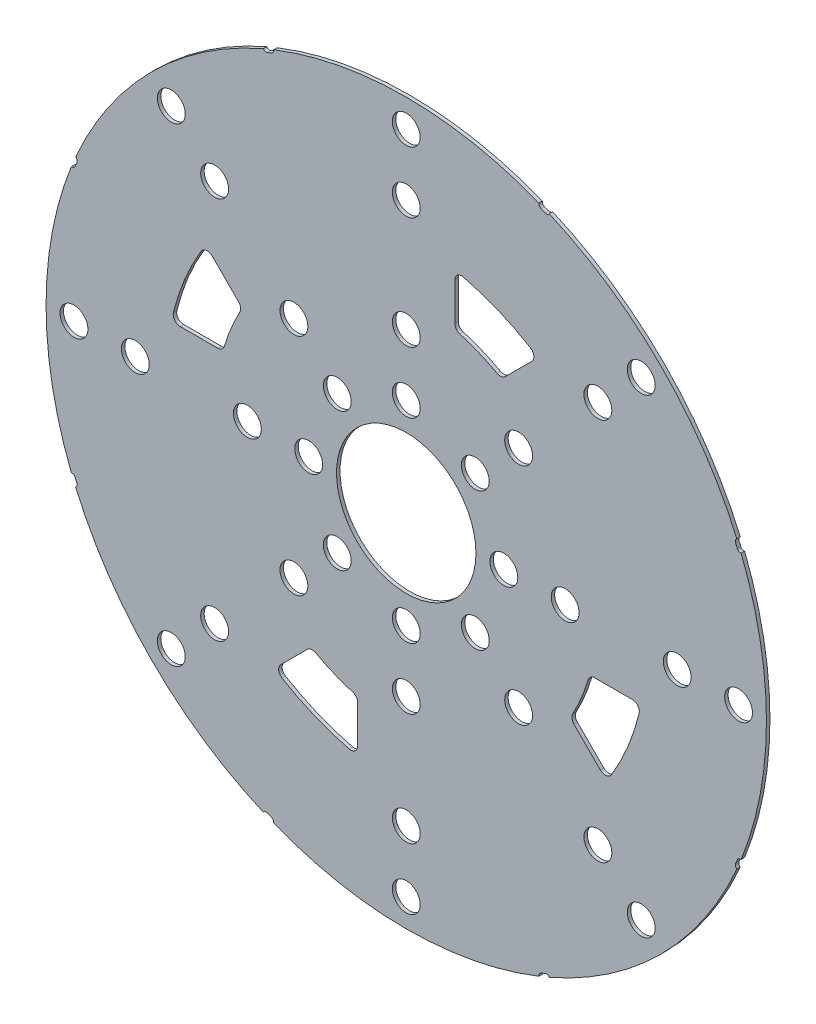
SolidWorks part; units mm, degrees
material "Epoxy, Unfilled"
ref_plane "Front Plane" through (0, 0, 0) normal (0, 0, 1) x (1, 0, 0)
ref_plane "Top Plane" through (0, 0, 0) normal (0, 1, 0) x (1, 0, 0)
ref_plane "Right Plane" through (0, 0, 0) normal (1, 0, 0) x (0, 0, -1)
sketch "Sketch4" plane through (0, 0, 0) normal (0, 0, 1) x (1, 0, 0)
  circle A0 centre (0, 0) radius 82.042
  dimension "D1" = 164.084
extrude "Boss-Extrude2" add sketch "Sketch4" along normal blind 0.7937
sketch "Sketch5" plane through (0, 0, 0.7937) normal (0, 0, 1) x (1, 0, 0)
  circle A0 centre (0, 0) radius 15.875
  dimension "D1" = 31.75
extrude "Cut-Extrude5" cut sketch "Sketch5" against normal through all
sketch "Sketch8" plane through (0, 0, 0.7937) normal (0, 0, 1) x (1, 0, 0)
  line L2 (76.8696, 30.4658) -> (75.8976, 32.8124)
  line L3 (76.8696, 30.4658) -> (75.6963, 29.9798)
  line L4 (75.6963, 29.9798) -> (74.7243, 32.3264)
  line L5 (75.8976, 32.8124) -> (74.7243, 32.3264)
  line L6 (0, 0) -> (82.042, 0) construction
  line L7 (-30.4658, 76.8696) -> (-32.8124, 75.8976)
  line L8 (-30.4658, 76.8696) -> (-29.9798, 75.6963)
  line L9 (-32.8124, 75.8976) -> (-32.3264, 74.7243)
  line L10 (-29.9798, 75.6963) -> (-32.3264, 74.7243)
  line L11 (-32.8124, 75.8976) -> (-29.9798, 75.6963) construction
  line L12 (-30.4658, 76.8696) -> (-32.3264, 74.7243) construction
  line L13 (-75.8976, 32.8124) -> (-76.8696, 30.4658)
  line L14 (-75.8976, 32.8124) -> (-74.7243, 32.3264)
  line L15 (-74.7243, 32.3264) -> (-75.6963, 29.9798)
  line L16 (-76.8696, 30.4658) -> (-75.6963, 29.9798)
  line L17 (-75.8976, 32.8124) -> (-75.6963, 29.9798) construction
  line L18 (-76.8696, 30.4658) -> (-74.7243, 32.3264) construction
  line L19 (-76.8696, -30.4658) -> (-75.8976, -32.8124)
  line L20 (-76.8696, -30.4658) -> (-75.6963, -29.9798)
  line L21 (-75.6963, -29.9798) -> (-74.7243, -32.3264)
  line L22 (-75.8976, -32.8124) -> (-74.7243, -32.3264)
  line L23 (-76.8696, -30.4658) -> (-74.7243, -32.3264) construction
  line L24 (-75.8976, -32.8124) -> (-75.6963, -29.9798) construction
  line L25 (-32.8124, -75.8976) -> (-30.4658, -76.8696)
  line L26 (-32.8124, -75.8976) -> (-32.3264, -74.7243)
  line L27 (-32.3264, -74.7243) -> (-29.9798, -75.6963)
  line L28 (-30.4658, -76.8696) -> (-29.9798, -75.6963)
  line L29 (-32.8124, -75.8976) -> (-29.9798, -75.6963) construction
  line L30 (-30.4658, -76.8696) -> (-32.3264, -74.7243) construction
  line L31 (30.4658, -76.8696) -> (32.8124, -75.8976)
  line L32 (30.4658, -76.8696) -> (29.9798, -75.6963)
  line L33 (29.9798, -75.6963) -> (32.3264, -74.7243)
  line L34 (32.8124, -75.8976) -> (32.3264, -74.7243)
  line L35 (30.4658, -76.8696) -> (32.3264, -74.7243) construction
  line L36 (32.8124, -75.8976) -> (29.9798, -75.6963) construction
  line L37 (75.8976, -32.8124) -> (76.8696, -30.4658)
  line L38 (75.8976, -32.8124) -> (74.7243, -32.3264)
  line L39 (74.7243, -32.3264) -> (75.6963, -29.9798)
  line L40 (76.8696, -30.4658) -> (75.6963, -29.9798)
  line L41 (75.8976, -32.8124) -> (75.6963, -29.9798) construction
  line L42 (76.8696, -30.4658) -> (74.7243, -32.3264) construction
  line L43 (76.8696, 30.4658) -> (74.7243, 32.3264) construction
  line L44 (75.8976, 32.8124) -> (75.6963, 29.9798) construction
  line L45 (32.8124, 75.8976) -> (30.4658, 76.8696)
  line L46 (32.8124, 75.8976) -> (32.3264, 74.7243)
  line L47 (32.3264, 74.7243) -> (29.9798, 75.6963)
  line L48 (30.4658, 76.8696) -> (29.9798, 75.6963)
  line L49 (32.8124, 75.8976) -> (29.9798, 75.6963) construction
  line L50 (30.4658, 76.8696) -> (32.3264, 74.7243) construction
  circle A0 centre (0, 0) radius 82.042 construction
  point P3 (-31.3961, 75.7969)
  point P11 (-75.7969, 31.3961)
  point P15 (75.7969, 31.3961)
  point P20 (-75.7969, -31.3961)
  point P25 (-31.3961, -75.7969)
  point P26 (0, 0)
  point P31 (31.3961, -75.7969)
  point P36 (75.7969, -31.3961)
  point P45 (31.3961, 75.7969)
  point P46 (0, 0)
  dimension "D3" = 0.635
  dimension "D5" = 1.27
  dimension "D6" = 2.54
  dimension "D7" = 1.27
  dimension "D9" = 0.635
  dimension "D10" = 112.5
  dimension "D14" = 0.635
  dimension "D21" = 22.5
  dimension "D11" = 8
extrude "Cut-Extrude11" cut sketch "Sketch8" against normal through all
sketch "Sketch9" plane through (0, 0, 0.7937) normal (0, 0, 1) x (1, 0, 0)
  line L0 (0, 0) -> (75.692, 0) construction
  line L1 (0, 0) -> (53.5223, 53.5223) construction
  line L2 (0, 0) -> (53.5223, -53.5223) construction
  line L3 (21.7035, 37.3292) -> (30.0037, 45.6293)
  line L4 (11.049, 41.7424) -> (11.049, 53.4806)
  line L5 (41.7424, -11.049) -> (53.4806, -11.049)
  line L6 (37.3292, -21.7035) -> (45.6293, -30.0037)
  line L7 (-11.049, -41.7424) -> (-11.049, -53.4806)
  line L8 (-21.7035, -37.3292) -> (-30.0037, -45.6293)
  line L9 (-41.7424, 11.049) -> (-53.4806, 11.049)
  line L10 (-37.3292, 21.7035) -> (-45.6293, 30.0037)
  circle A0 centre (22.225, 0) radius 3.175
  circle A1 centre (36.195, 0) radius 3.175
  circle A2 centre (61.722, 0) radius 3.175
  circle A3 centre (75.692, 0) radius 3.175
  circle A4 centre (0, 0) radius 15.875 construction
  arc A5 (21.7035, 37.3292) -> (11.049, 41.7424) centre (0, 0) ccw
  circle A6 centre (15.7154, -15.7154) radius 3.175
  circle A7 centre (25.5937, -25.5937) radius 3.175
  circle A8 centre (43.644, -43.644) radius 3.175
  circle A9 centre (53.5223, -53.5223) radius 3.175
  circle A10 centre (0, -22.225) radius 3.175
  circle A11 centre (0, -36.195) radius 3.175
  circle A12 centre (0, -61.722) radius 3.175
  circle A13 centre (0, -75.692) radius 3.175
  circle A14 centre (-15.7154, -15.7154) radius 3.175
  circle A15 centre (-25.5937, -25.5937) radius 3.175
  circle A16 centre (-43.644, -43.644) radius 3.175
  circle A17 centre (-53.5223, -53.5223) radius 3.175
  circle A18 centre (-22.225, 0) radius 3.175
  circle A19 centre (-36.195, 0) radius 3.175
  circle A20 centre (-61.722, 0) radius 3.175
  circle A21 centre (-75.692, 0) radius 3.175
  circle A22 centre (-15.7154, 15.7154) radius 3.175
  circle A23 centre (-25.5937, 25.5937) radius 3.175
  circle A24 centre (-43.644, 43.644) radius 3.175
  circle A25 centre (-53.5223, 53.5223) radius 3.175
  circle A26 centre (0, 22.225) radius 3.175
  circle A27 centre (0, 36.195) radius 3.175
  circle A28 centre (0, 61.722) radius 3.175
  circle A29 centre (0, 75.692) radius 3.175
  circle A30 centre (15.7154, 15.7154) radius 3.175
  circle A31 centre (25.5937, 25.5937) radius 3.175
  circle A32 centre (43.644, 43.644) radius 3.175
  circle A33 centre (53.5223, 53.5223) radius 3.175
  arc A34 (30.0037, 45.6293) -> (11.049, 53.4806) centre (0, 0) ccw
  arc A35 (45.6293, -30.0037) -> (53.4806, -11.049) centre (0, 0) ccw
  arc A36 (37.3292, -21.7035) -> (41.7424, -11.049) centre (0, 0) ccw
  arc A37 (-30.0037, -45.6293) -> (-11.049, -53.4806) centre (0, 0) ccw
  arc A38 (-21.7035, -37.3292) -> (-11.049, -41.7424) centre (0, 0) ccw
  arc A39 (-45.6293, 30.0037) -> (-53.4806, 11.049) centre (0, 0) ccw
  arc A40 (-37.3292, 21.7035) -> (-41.7424, 11.049) centre (0, 0) ccw
  point P74 (0, 0)
  point P87 (0, 0)
  dimension "D3" = 6.35
  dimension "D6" = 43.18
  dimension "D10" = 54.61
  dimension "D1" = 13.97
  dimension "D2" = 13.97
  dimension "D4" = 6.35
  dimension "D8" = 45
  dimension "D9" = 45
  dimension "D5" = 25.527
  dimension "D11" = 11.049
  dimension "D12" = 11.049
  dimension "D7" = 8
  dimension "D13" = 4
extrude "Cut-Extrude12" cut sketch "Sketch9" against normal through all
fillet "Fillet1" radius 1.5875 16 edges at (11.049, 53.4806, 0.3969) (11.049, 41.7424, 0.3969) (30.0037, 45.6293, 0.3969) (21.7035, 37.3292, 0.3969) (45.6293, -30.0037, 0.3969) (37.3292, -21.7035, 0.3969) (41.7424, -11.049, 0.3969) (53.4806, -11.049, 0.3969) (-11.049, -41.7424, 0.3969) (-30.0037, -45.6293, 0.3969) (-21.7035, -37.3292, 0.3969) (-11.049, -53.4806, 0.3969) (-41.7424, 11.049, 0.3969) (-53.4806, 11.049, 0.3969) (-37.3292, 21.7035, 0.3969) (-45.6293, 30.0037, 0.3969)
fillet "Fillet2" radius 0.7937 16 edges at (-75.6963, 29.9798, 0.3969) (-29.9798, 75.6963, 0.3969) (-32.3264, 74.7243, 0.3969) (-74.7243, 32.3264, 0.3969) (-74.7243, -32.3264, 0.3969) (-75.6963, -29.9798, 0.3969) (-29.9798, -75.6963, 0.3969) (-32.3264, -74.7243, 0.3969) (29.9798, -75.6963, 0.3969) (32.3264, -74.7243, 0.3969) (75.6963, -29.9798, 0.3969) (74.7243, -32.3264, 0.3969) (75.6963, 29.9798, 0.3969) (74.7243, 32.3264, 0.3969) (32.3264, 74.7243, 0.3969) (29.9798, 75.6963, 0.3969)
equation "\"CoilSep\"= 1.005"
equation "\"D5@Sketch9\"=\"CoilSep\""
